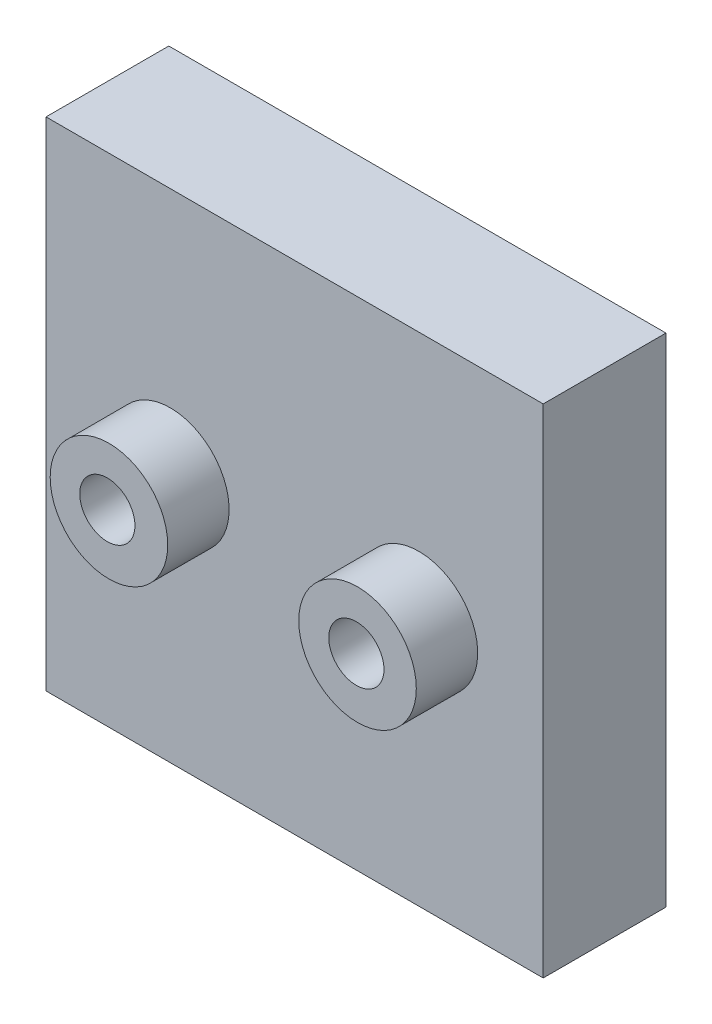
SolidWorks part; units mm, degrees
ref_plane "Front Plane" through (0, 0, 0) normal (0, 0, 1) x (1, 0, 0)
ref_plane "Top Plane" through (0, 0, 0) normal (0, 1, 0) x (1, 0, 0)
ref_plane "Right Plane" through (0, 0, 0) normal (1, 0, 0) x (0, 0, -1)
sketch "Sketch1" plane through (0, 0, 0) normal (0, 1, 0) x (1, 0, 0)
  line L0 (0, 0) -> (0, 78.8911) construction
  line L2 (-40.5, 10) -> (40.5, 10)
  line L3 (-40.5, 10) -> (-40.5, -10)
  line L4 (-40.5, -10) -> (40.5, -10)
  line L5 (40.5, 10) -> (40.5, -10)
  line L6 (-40.5, 10) -> (40.5, -10) construction
  line L7 (-40.5, -10) -> (40.5, 10) construction
  dimension "D1" = 81
  dimension "D2" = 20
extrude "Boss-Extrude2" add sketch "Sketch1" along normal blind 81 contours L2 L5 L4 L3
sketch "Sketch2" plane through (0, 0, 10) normal (0, 0, 1) x (1, 0, 0)
  circle A0 centre (-20.25, 40.5) radius 9.5758
  circle A1 centre (20.25, 40.5) radius 9.5758
  point P2 (0, 0)
extrude "Boss-Extrude4" add sketch "Sketch2" along normal blind 10
sketch "Sketch4" plane through (0, 0, 20) normal (0, 0, 1) x (1, 0, 0)
  circle A0 centre (-20.5109, 40.5563) radius 4.4958
  circle A1 centre (20.0601, 40.5563) radius 4.4958
extrude "Cut-Extrude1" cut sketch "Sketch4" against normal blind 10
